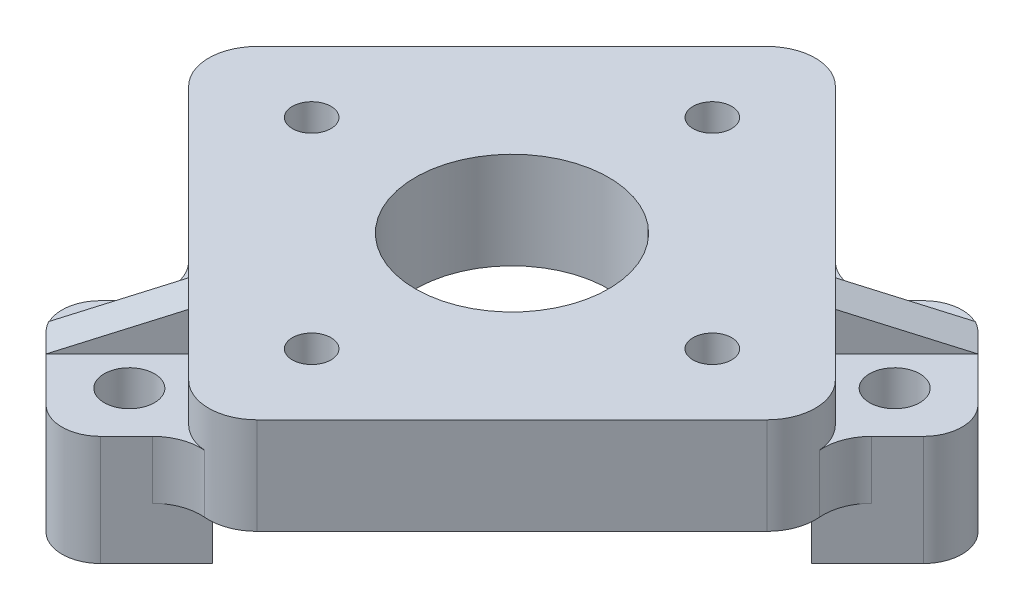
SolidWorks part; units mm, degrees
ref_plane "Front Plane" through (0, 0, 0) normal (0, 0, 1) x (1, 0, 0)
ref_plane "Top Plane" through (0, 0, 0) normal (0, 1, 0) x (1, 0, 0)
ref_plane "Right Plane" through (0, 0, 0) normal (1, 0, 0) x (0, 0, -1)
sketch "Sketch1" plane through (0, 0, 0) normal (0, 1, 0) x (1, 0, 0)
  line L0 (0, 10.365) -> (0, -10.365) construction
  line L1 (10.365, 0) -> (-10.365, 0) construction
  line L2 (0, 10.365) -> (10.365, 0) construction
  line L3 (10.365, 0) -> (0, -10.365) construction
  line L4 (0, -10.365) -> (-10.365, 0) construction
  line L8 (-10.365, 0) -> (0, 10.365) construction
  line L9 (1.7678, 14.9612) -> (14.9612, 1.7678)
  line L10 (14.9612, -1.7678) -> (1.7678, -14.9612)
  line L11 (-1.7678, -14.9612) -> (-14.9612, -1.7678)
  line L12 (-14.9612, 1.7678) -> (-1.7678, 14.9612)
  line L13 (16.729, 0) -> (0, -16.729) construction
  line L14 (0, -16.729) -> (-16.729, 0) construction
  line L15 (0, 16.729) -> (16.729, 0) construction
  line L16 (-16.729, 0) -> (0, 16.729) construction
  circle A7 centre (0, 10.365) radius 0.5
  circle A8 centre (0, -10.365) radius 0.5
  circle A9 centre (10.365, 0) radius 0.5
  circle A10 centre (-10.365, 0) radius 0.5
  circle A11 centre (0, 0) radius 5
  arc A12 (1.7678, -14.9612) -> (-1.7678, -14.9612) centre (0, -13.1934) cw
  arc A13 (14.9612, 1.7678) -> (14.9612, -1.7678) centre (13.1934, 0) cw
  arc A14 (-14.9612, -1.7678) -> (-14.9612, 1.7678) centre (-13.1934, 0) cw
  arc A15 (1.7678, 14.9612) -> (-1.7678, 14.9612) centre (0, 13.1934) ccw
  dimension "D2" = 1
  dimension "D3" = 10
  dimension "D4" = 4.5
  dimension "D5" = 2.5
  dimension "D1" = 20.73
extrude "Boss-Extrude1" add sketch "Sketch1" along normal blind 5
sketch "Sketch4" plane through (0, 0, 0) normal (0, -1, 0) x (1, 0, 0)
  circle A0 centre (0, 10.365) radius 3
  circle A1 centre (10.365, 0) radius 3
  circle A2 centre (-10.365, 0) radius 3
  circle A3 centre (0, -10.365) radius 3
  point P0 (0, 10.365)
  point P3 (10.365, 0)
  point P6 (-10.365, 0)
  point P9 (0, -10.365)
  dimension "D1" = 6
ref_plane "Plane1" through (0, -2.7, 0) normal (0, 1, 0) x (1, 0, 0)
ref_plane "Plane2" through (8.3645, 0, 8.3645) normal (0.7071, 0, 0.7071) x (0.7071, 0, -0.7071)
ref_plane "Plane3" through (2.7076, 0, 2.7076) normal (0.7071, 0, 0.7071) x (0.7071, 0, -0.7071)
sketch "Sketch3" plane through (0, -2.7, 0) normal (0, 1, 0) x (1, 0, 0)
  line L0 (-8.3645, 8.3645) -> (8.3645, -8.3645) construction
  line L1 (-1.7678, 14.9612) -> (-14.9612, 1.7678) construction
  line L2 (1.7678, -14.9612) -> (14.9612, -1.7678) construction
  line L3 (9.8995, 9.8995) -> (14.8492, 4.9497) construction
  line L5 (10.5375, 4.9497) -> (14.8492, 0.638)
  line L12 (14.9612, 1.7678) -> (1.7678, 14.9612) construction
  line L13 (14.8492, 0.638) -> (19.161, 4.9497)
  line L20 (0, 0) -> (9.8995, 9.8995) construction
  line L21 (14.9612, 1.7678) -> (1.7678, 14.9612) construction
  line L22 (19.161, 4.9497) -> (14.8492, 9.2615)
  line L23 (14.8492, 9.2615) -> (10.5375, 4.9497)
  line L24 (19.161, 4.9497) -> (10.5375, 4.9497) construction
  line L25 (-4.9497, -19.161) -> (-4.9497, -10.5375) construction
  line L26 (-9.8995, -9.8995) -> (-4.9497, -14.8492) construction
  line L27 (-9.2615, -14.8492) -> (-4.9497, -10.5375)
  line L28 (-4.9497, -19.161) -> (-9.2615, -14.8492)
  line L29 (-0.638, -14.8492) -> (-4.9497, -19.161)
  line L30 (-4.9497, -10.5375) -> (-0.638, -14.8492)
  line L31 (10.5375, 4.9497) -> (8.7697, 6.7175)
  line L32 (8.7697, 6.7175) -> (13.0815, 11.0293)
  line L33 (13.0815, 11.0293) -> (14.8492, 9.2615)
  line L34 (-4.9497, -10.5375) -> (-6.7175, -8.7697)
  line L35 (-6.7175, -8.7697) -> (-11.0293, -13.0815)
  line L36 (-11.0293, -13.0815) -> (-9.2615, -14.8492)
  circle A2 centre (14.8492, 4.9497) radius 1.3
  circle A3 centre (-4.9497, -14.8492) radius 1.3
  dimension "D1" = 2.6
  dimension "D2" = 7
  dimension "D3" = 3.0489
  dimension "D4" = 14
  dimension "D5" = 2.5
extrude "Boss-Extrude4" add sketch "Sketch3" along normal offset from surface (5.7 mm away) 3 contours L30 L27 L28 L29 A3 | L35 L36 L27 L34 | L22 L23 L5 L13 A2 | L33 L32 L31 L23 region at (12.7796, -2.7, -7.0194) region at (11.8095, -2.7, -7.9895) region at (-7.9895, -2.7, 11.8095) region at (-7.0194, -2.7, 12.7796) up to face at (-10.365, 0, 0.5)
sketch "Sketch7" plane through (2.7076, 0, 2.7076) normal (0.7071, 0, 0.7071) x (0.7071, 0, -0.7071)
  line L0 (11.8292, 5) -> (17.0489, 3)
  line L1 (-11.8292, 5) -> (-17.0489, 3)
  line L2 (-17.0489, 3) -> (-11.8292, 3)
  line L3 (-11.8292, 3) -> (-11.8292, 5)
  line L4 (11.8292, 5) -> (11.8292, 3)
  line L5 (11.8292, 3) -> (17.0489, 3)
extrude "Boss-Extrude6" add sketch "Sketch7" along normal mid plane 2
fillet "Fillet1" radius 2.5 4 edges at (-7.3384, 1.5, 9.3906) (9.3906, 1.5, -7.3384) (15.3953, 1.5, -1.184) (-1.184, 1.5, 15.3953)
fillet "Fillet2" radius 2 4 edges at (-11.0293, 0.15, 13.0815) (-4.9497, 0.15, 19.161) (13.0815, 0.15, -11.0293) (19.161, 0.15, -4.9497)
hole_wizard "Ø2.0mm Dowel Hole1" positions "Sketch4" profile "Sketch11" hole size "Ø2.0" standard "ANSI Metric"
sketch "Sketch11" plane through (0, 0, 10.365) normal (1, 0, 0) x (0, 0, -1)
  line L0 (0, 0) -> (0, 43.5309)
  line L1 (0, 43.5309) -> (1, 42.93)
  line L2 (1, 42.93) -> (1, 0)
  line L5 (1, 0) -> (0, 0)
  line L10 (0, 43.5309) -> (-1, 42.93) construction
  line L11 (0, -6.35) -> (0, 107.95) construction
  dimension "Hole Dia." = 2
  dimension "Hole Depth" = 42.93
  dimension "Drill Angle" = 118
